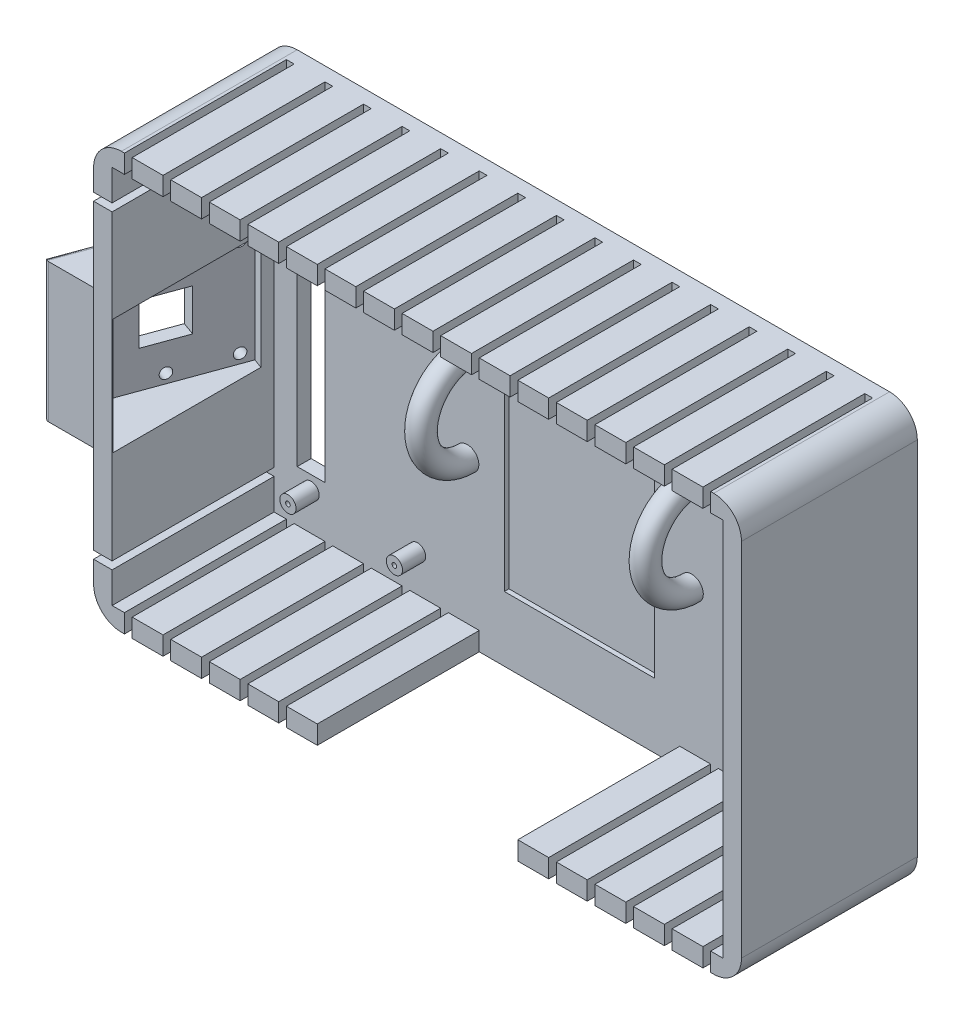
SolidWorks part; units mm, degrees
material "PLA"
ref_plane "Front Plane" through (0, 0, 0) normal (1, 0, 0) x (0, 1, 0)
ref_plane "Top Plane" through (0, 0, 0) normal (0, 0, 1) x (0, 1, 0)
ref_plane "Right Plane" through (0, 0, 0) normal (0, 1, 0) x (-1, 0, 0)
sketch "Sketch1" plane through (0, 0, 0) normal (0, 0, 1) x (0, 1, 0)
  line L0 (-45, 0) -> (45, 0) construction
  line L1 (45, -70) -> (-45, -70)
  line L2 (45, -70) -> (45, 70)
  line L3 (45, 70) -> (-45, 70)
  line L4 (-45, -70) -> (-45, 70)
  line L5 (0, 70) -> (0, -70) construction
  point P9 (0, 0)
  dimension "D1" = 140
  dimension "D2" = 90
extrude "Boss-Extrude1" add sketch "Sketch1" along normal blind 3
sketch "Sketch2" plane through (0, 0, 3) normal (0, 0, 1) x (1, 0, 0)
  line L0 (-70, 45) -> (-70, -45) construction
  line L1 (-16.25, 31) -> (16.25, 31)
  line L2 (-16.25, 31) -> (-16.25, -31)
  line L3 (-16.25, -31) -> (16.25, -31)
  line L4 (16.25, 31) -> (16.25, -31)
  line L6 (-70, 0) -> (-16.25, 0) construction
  line L7 (16.25, 0) -> (70, 0) construction
  line L8 (70, -45) -> (70, 45) construction
  line L9 (0, 31) -> (0, 45) construction
  line L10 (70, 45) -> (-70, 45) construction
  line L11 (0, -31) -> (0, -45) construction
  line L12 (-70, -45) -> (70, -45) construction
  dimension "D1" = 62
  dimension "D2" = 32.5
extrude "Cut-Extrude1" cut sketch "Sketch2" against normal blind 1
sketch "Sketch6" plane through (0, 0, 3) normal (0, 0, 1) x (1, 0, 0)
  line L0 (-70, -45) -> (70, -45) construction
  line L2 (-58, 25) -> (-58, 45) construction
  line L3 (70, 45) -> (-70, 45) construction
  circle A0 centre (-58, 25) radius 1.75
  circle A1 centre (-35, 25) radius 1.75
  circle A2 centre (-35, -33) radius 1.75
  circle A3 centre (-58, -33) radius 1.75
  circle A4 centre (-58, 25) radius 0.5
  circle A5 centre (-35, 25) radius 0.5
  circle A6 centre (-58, -33) radius 0.5
  circle A7 centre (-35, -33) radius 0.5
  dimension "D1" = 3.5
  dimension "D2" = 23
  dimension "D3" = 58
  dimension "D4" = 12
  dimension "D5" = 1
extrude "Boss-Extrude2" add sketch "Sketch6" along normal blind 5 contours A1 | A0 | A3 | A2 region at (-59.7005, 25, 3) region at (-36.7005, 25, 3) region at (-36.7005, -33, 3) region at (-59.7005, -33, 3)
extrude "Boss-Extrude3" add sketch "Sketch6<3>" along normal blind 4 contours A4 | A5 | A6 | A7 region at (-58, 25, 3) region at (-35, 25, 3) region at (-58, -33, 3) region at (-35, -33, 3)
sketch "Sketch6<3>" plane through (0, 0, 3) normal (0, 0, 1) x (1, 0, 0) same geometry as "Sketch6"
sketch "Sketch7" plane through (0, 0, 3) normal (0, 0, 1) x (1, 0, 0)
  line L0 (-61.6667, 45) -> (-61.6667, 41)
  line L1 (-70, 45) -> (-63.3333, 45)
  line L2 (-70, 45) -> (-70, 41)
  line L3 (-70, 41) -> (-63.3333, 41)
  line L4 (-63.3333, 45) -> (-63.3333, 41)
  line L5 (-61.6667, 45) -> (-55, 45)
  line L6 (-55, 45) -> (-55, 41)
  line L7 (-61.6667, 41) -> (-55, 41)
  line L8 (-53.3333, 45) -> (-53.3333, 41)
  line L9 (-53.3333, 45) -> (-46.6667, 45)
  line L10 (-46.6667, 45) -> (-46.6667, 41)
  line L11 (-53.3333, 41) -> (-46.6667, 41)
  line L12 (-45, 45) -> (-45, 41)
  line L13 (-45, 45) -> (-38.3333, 45)
  line L14 (-38.3333, 45) -> (-38.3333, 41)
  line L15 (-45, 41) -> (-38.3333, 41)
  line L16 (-36.6667, 45) -> (-36.6667, 41)
  line L17 (-36.6667, 45) -> (-30, 45)
  line L18 (-30, 45) -> (-30, 41)
  line L19 (-36.6667, 41) -> (-30, 41)
  line L20 (-28.3333, 45) -> (-28.3333, 41)
  line L21 (-28.3333, 45) -> (-21.6667, 45)
  line L22 (-21.6667, 45) -> (-21.6667, 41)
  line L23 (-28.3333, 41) -> (-21.6667, 41)
  line L24 (-20, 45) -> (-20, 41)
  line L25 (-20, 45) -> (-13.3333, 45)
  line L26 (-13.3333, 45) -> (-13.3333, 41)
  line L27 (-20, 41) -> (-13.3333, 41)
  line L28 (-11.6667, 45) -> (-11.6667, 41)
  line L29 (-11.6667, 45) -> (-5, 45)
  line L30 (-5, 45) -> (-5, 41)
  line L31 (-11.6667, 41) -> (-5, 41)
  line L32 (-3.3333, 45) -> (-3.3333, 41)
  line L33 (-3.3333, 45) -> (3.3333, 45)
  line L34 (3.3333, 45) -> (3.3333, 41)
  line L35 (-3.3333, 41) -> (3.3333, 41)
  line L36 (5, 45) -> (5, 41)
  line L37 (5, 45) -> (11.6667, 45)
  line L38 (11.6667, 45) -> (11.6667, 41)
  line L39 (5, 41) -> (11.6667, 41)
  line L40 (13.3333, 45) -> (13.3333, 41)
  line L41 (13.3333, 45) -> (20, 45)
  line L42 (20, 45) -> (20, 41)
  line L43 (13.3333, 41) -> (20, 41)
  line L44 (21.6667, 45) -> (21.6667, 41)
  line L45 (21.6667, 45) -> (28.3333, 45)
  line L46 (28.3333, 45) -> (28.3333, 41)
  line L47 (21.6667, 41) -> (28.3333, 41)
  line L48 (30, 45) -> (30, 41)
  line L49 (30, 45) -> (36.6667, 45)
  line L50 (36.6667, 45) -> (36.6667, 41)
  line L51 (30, 41) -> (36.6667, 41)
  line L52 (38.3333, 45) -> (38.3333, 41)
  line L53 (38.3333, 45) -> (45, 45)
  line L54 (45, 45) -> (45, 41)
  line L55 (38.3333, 41) -> (45, 41)
  line L56 (46.6667, 45) -> (46.6667, 41)
  line L57 (46.6667, 45) -> (53.3333, 45)
  line L58 (53.3333, 45) -> (53.3333, 41)
  line L59 (46.6667, 41) -> (53.3333, 41)
  line L60 (55, 45) -> (55, 41)
  line L61 (55, 45) -> (61.6667, 45)
  line L62 (61.6667, 45) -> (61.6667, 41)
  line L63 (55, 41) -> (61.6667, 41)
  line L64 (63.3333, 45) -> (63.3333, 41)
  line L65 (63.3333, 45) -> (70, 45)
  line L66 (70, 45) -> (70, 41)
  line L67 (63.3333, 41) -> (70, 41)
  line L112 (0, 0) -> (0, 18.2112) construction
  line L113 (0, 0) -> (-20.7335, 0) construction
  line L114 (13.3333, -45) -> (20, -45)
  line L115 (20, -45) -> (20, -41)
  line L116 (13.3333, -41) -> (20, -41)
  line L117 (13.3333, -45) -> (13.3333, -41)
  line L118 (21.6667, -45) -> (28.3333, -45)
  line L119 (28.3333, -45) -> (28.3333, -41)
  line L120 (21.6667, -41) -> (28.3333, -41)
  line L121 (21.6667, -45) -> (21.6667, -41)
  line L122 (30, -45) -> (36.6667, -45)
  line L123 (36.6667, -45) -> (36.6667, -41)
  line L124 (30, -41) -> (36.6667, -41)
  line L125 (30, -45) -> (30, -41)
  line L126 (38.3333, -45) -> (45, -45)
  line L127 (45, -45) -> (45, -41)
  line L128 (38.3333, -41) -> (45, -41)
  line L129 (38.3333, -45) -> (38.3333, -41)
  line L130 (46.6667, -45) -> (53.3333, -45)
  line L131 (53.3333, -45) -> (53.3333, -41)
  line L132 (46.6667, -41) -> (53.3333, -41)
  line L133 (46.6667, -45) -> (46.6667, -41)
  line L134 (55, -45) -> (61.6667, -45)
  line L135 (61.6667, -45) -> (61.6667, -41)
  line L136 (55, -41) -> (61.6667, -41)
  line L137 (55, -45) -> (55, -41)
  line L138 (63.3333, -45) -> (70, -45)
  line L139 (70, -45) -> (70, -41)
  line L140 (63.3333, -41) -> (70, -41)
  line L141 (63.3333, -45) -> (63.3333, -41)
  line L142 (5, -45) -> (11.6667, -45)
  line L143 (11.6667, -45) -> (11.6667, -41)
  line L144 (5, -41) -> (11.6667, -41)
  line L145 (5, -45) -> (5, -41)
  line L146 (-3.3333, -45) -> (3.3333, -45)
  line L147 (3.3333, -45) -> (3.3333, -41)
  line L148 (-3.3333, -41) -> (3.3333, -41)
  line L149 (-3.3333, -45) -> (-3.3333, -41)
  line L150 (-11.6667, -45) -> (-5, -45)
  line L151 (-5, -45) -> (-5, -41)
  line L152 (-11.6667, -41) -> (-5, -41)
  line L153 (-11.6667, -45) -> (-11.6667, -41)
  line L154 (-20, -45) -> (-13.3333, -45)
  line L155 (-13.3333, -45) -> (-13.3333, -41)
  line L156 (-20, -41) -> (-13.3333, -41)
  line L157 (-20, -45) -> (-20, -41)
  line L158 (-28.3333, -45) -> (-21.6667, -45)
  line L159 (-21.6667, -45) -> (-21.6667, -41)
  line L160 (-28.3333, -41) -> (-21.6667, -41)
  line L161 (-28.3333, -45) -> (-28.3333, -41)
  line L162 (-36.6667, -45) -> (-30, -45)
  line L163 (-30, -45) -> (-30, -41)
  line L164 (-36.6667, -41) -> (-30, -41)
  line L165 (-36.6667, -45) -> (-36.6667, -41)
  line L166 (-70, -41) -> (-63.3333, -41)
  line L167 (-63.3333, -45) -> (-63.3333, -41)
  line L168 (-70, -45) -> (-63.3333, -45)
  line L169 (-70, -45) -> (-70, -41)
  line L170 (-61.6667, -45) -> (-55, -45)
  line L171 (-55, -45) -> (-55, -41)
  line L172 (-61.6667, -41) -> (-55, -41)
  line L173 (-61.6667, -45) -> (-61.6667, -41)
  line L174 (-53.3333, -45) -> (-46.6667, -45)
  line L175 (-46.6667, -45) -> (-46.6667, -41)
  line L176 (-53.3333, -41) -> (-46.6667, -41)
  line L177 (-53.3333, -45) -> (-53.3333, -41)
  line L178 (-45, -45) -> (-38.3333, -45)
  line L179 (-38.3333, -45) -> (-38.3333, -41)
  line L180 (-45, -41) -> (-38.3333, -41)
  line L181 (-45, -45) -> (-45, -41)
  line L226 (-70, 32.6633) -> (-60.5263, 32.6633) construction
  line L227 (-70, -32.6633) -> (-61.2912, -32.6633) construction
  line L228 (-70, 45) -> (-70, -45) construction
  line L229 (-70, 32.6633) -> (-66, 32.6633)
  line L230 (-70, 32.6633) -> (-70, -32.6633)
  line L231 (-70, -32.6633) -> (-66, -32.6633)
  line L232 (-66, 32.6633) -> (-66, -32.6633)
  line L233 (70, 45) -> (66, 45)
  line L234 (70, 45) -> (70, -45)
  line L235 (70, -45) -> (66, -45)
  line L236 (66, 45) -> (66, -45)
  line L237 (-70, 41) -> (-66, 41)
  line L238 (-70, 41) -> (-70, 34.3333)
  line L239 (-70, 34.3333) -> (-66, 34.3333)
  line L240 (-66, 41) -> (-66, 34.3333)
  line L246 (-70, -34.3333) -> (-66, -34.3333)
  line L247 (-70, -34.3333) -> (-70, -41)
  line L248 (-70, -41) -> (-66, -41)
  line L249 (-66, -34.3333) -> (-66, -41)
  line M13 (70, 45) -> (-70, 45)
  line M14 (-70, 45) -> (-70, -45)
  line M15 (-70, -45) -> (70, -45)
  line M16 (70, -45) -> (70, 45)
  dimension "D1" = 6.6667
  dimension "D2" = 4
  dimension "D6" = 1.67
  dimension "D4" = 4
  dimension "D7" = 1.67
  dimension "D3" = 17
sketch "Sketch9" plane through (0, 0, 3) normal (0, 0, 1) x (1, 0, 0)
  line L0 (-36.3093, 0) -> (22.5747, 0) construction
  line L1 (0, 0) -> (0, 22.2066) construction
  line L2 (-16.25, 31) -> (-16.25, -31) construction
  circle A0 centre (-24.25, -10) radius 2.5
  circle A1 centre (24.25, -10) radius 2.5
  dimension "D1" = 5
  dimension "D2" = 10
  dimension "D3" = 8
revolve "Revolve3" add sketch "Sketch9" angle 180 about L0 reverse direction yes
extrude "Boss-Extrude8" add sketch "Sketch7" along normal blind 35 contours L167 L166 M15 M14 | L173 L171 L172 M15 | L177 L175 L176 M15 | L181 L179 L180 M15 | L165 L163 L164 M15 | L161 L159 L160 M15 | L157 L155 L156 M15 | L153 L151 L152 M15 | L149 L147 L148 M15 | L145 L143 L144 M15 | L121 L119 L120 M15 | L125 L123 L124 M15 | L129 L127 L128 M15 | L133 L131 L132 M15 | L137 L135 L136 M15 | L140 L236 L138 M16 | L67 L236 L140 M16 | L60 L63 L62 M13 | L56 L59 L58 M13 | L48 L51 L50 M13 | L32 L35 L34 M13 | L28 L31 L30 M13 | L24 L27 L26 M13 | L20 L23 L22 M13 | L16 L19 L18 M13 | L0 L7 L6 M13 | L4 L3 M13 M14 | L240 L237 L239 M14 | L116 L115 L114 L117 | L138 L141 L140 L139 | L66 L67 L64 L65 | L53 L54 L55 L52 | L44 L47 L46 L45 | L42 L43 L40 L41 | L36 L39 L38 L37 | L28 L31 L30 L29 | L13 L14 L15 L12 | L9 L10 L11 L8 | L230 L231 L232 L229 | L247 L248 L249 L246 region at (-58.3333, 43, 3) region at (-66.6667, 43, 3) region at (-68, 37.6667, 3) region at (-33.3333, 43, 3) region at (-25, 43, 3) region at (-66.6667, -43, 3) region at (-16.6667, 43, 3) region at (-58.3333, -43, 3) region at (-8.3333, 43, 3) region at (-50, -43, 3) region at (0, 43, 3) region at (-41.6667, -43, 3) region at (-33.3333, -43, 3) region at (-25, -43, 3) region at (-16.6667, -43, 3) region at (33.3333, 43, 3) region at (-8.3333, -43, 3) region at (0, -43, 3) region at (50, 43, 3) region at (8.3333, -43, 3) region at (58.3333, 43, 3) region at (25, -43, 3) region at (68, 0, 3) region at (68, -43, 3) region at (33.3333, -43, 3) region at (41.6667, -43, 3) region at (58.3333, -43, 3) region at (50, -43, 3)
sketch "Sketch18" plane through (0, 0, 0) normal (0, 1, 0) x (-1, 0, 0)
  line L0 (70, 36.5) -> (82.6547, 36.5)
  line L1 (70, 38) -> (70, 0) construction
  line L2 (82.6547, 36.5) -> (70, 1.7314)
  line L3 (70, 1.7314) -> (70, 36.5)
  line L4 (63.3333, 38) -> (70, 38) construction
  dimension "D1" = 20
  dimension "D2" = 37
  dimension "D3" = 1.5
extrude "Boss-Extrude9" add sketch "Sketch18" along normal blind 15 and the other way blind 15
sketch "Sketch19" plane through (-61.2551, 0, -22.295) normal (-0.9397, 0, -0.342) x (0, -1, 0)
  line L0 (-10.5, 43.0684) -> (-10.5, 30.5684) construction
  line L1 (4.5, 38.5684) -> (-4.5, 38.5684)
  line L2 (4.5, 38.5684) -> (4.5, 47.5684)
  line L3 (4.5, 47.5684) -> (-4.5, 47.5684)
  line L4 (-4.5, 38.5684) -> (-4.5, 47.5684)
  line L5 (10.5, 43.0684) -> (10.5, 30.5684) construction
  line L6 (-10.5, 43.0684) -> (10.5, 43.0684) construction
  line L7 (-10.5, 30.5684) -> (10.5, 30.5684) construction
  line L8 (0, 43.0684) -> (0, 30.5684) construction
  line L9 (-15, 25.5684) -> (-15, 62.5684) construction
  line L10 (15, 25.5684) -> (15, 62.5684) construction
  line L14 (15, 25.5684) -> (-15, 25.5684) construction
  circle A0 centre (-10.5, 43.0684) radius 1.15
  circle A1 centre (10.5, 43.0684) radius 1.15
  circle A2 centre (10.5, 30.5684) radius 1.15
  circle A3 centre (-10.5, 30.5684) radius 1.15
  circle A4 centre (0, 43.0684) radius 1
  point P15 (0, 47.5684)
  point P16 (4.5, 43.0684)
  dimension "D1" = 2.3
  dimension "D3" = 21
  dimension "D4" = 12.5
  dimension "D6" = 2
  dimension "D2" = 9
  dimension "D5" = 5
extrude "Cut-Extrude2" cut sketch "Sketch19" against normal up to next contours A4 | L4 L1 L2 L3 A4 | A0 | A3 | A2 | A1 region at (-74.4898, 0, 14.067) region at (-75.9854, 10.5, 18.176) region at (-75.9854, -10.5, 18.176) region at (-71.7101, -10.5, 6.4298) region at (-71.7101, 10.5, 6.4298) region at (-75.9854, 0, 18.176)
sketch "Sketch21" plane through (-61.2551, 0, -22.295) normal (-0.9397, 0, -0.342) x (0, -1, 0)
  line L0 (0, 62.5684) -> (0, 25.5684) construction
  line L1 (-12.5, 58.0684) -> (12.5, 58.0684)
  line L2 (-12.5, 58.0684) -> (-12.5, 28.0684)
  line L3 (-12.5, 28.0684) -> (12.5, 28.0684)
  line L4 (12.5, 58.0684) -> (12.5, 28.0684)
  line L5 (15, 62.5684) -> (-15, 62.5684) construction
  line L6 (15, 25.5684) -> (-15, 25.5684) construction
  circle A0 centre (-10.5, 30.5684) radius 1.15 construction
  dimension "D3" = 2.5
  dimension "D1" = 25
  dimension "D2" = 30
extrude "Cut-Extrude5" cut sketch "Sketch21" against normal up to next from offset 3 offset against normal yes
sketch "Sketch22" plane through (0, 0, 3) normal (0, 0, 1) x (1, 0, 0)
  line L0 (-16.25, 39) -> (16.25, 39)
  line L1 (-16.25, 39) -> (-16.25, 33)
  line L2 (16.25, 39) -> (16.25, 33)
  line L3 (-16.25, 33) -> (16.25, 33)
  line L4 (-16.25, 39) -> (16.25, 33) construction
  line L5 (16.25, 39) -> (-16.25, 33) construction
  line L6 (16.25, 31) -> (-16.25, 31) construction
  line L7 (-3.3333, 45) -> (-5, 45) construction
  point P1 (0, 36)
  dimension "D1" = 6
  dimension "D2" = 6
extrude "Cut-Extrude6" cut sketch "Sketch22" against normal through all
sketch "Sketch23" plane through (0, -45, 0) normal (0, -1, 0) x (1, 0, 0)
  line L0 (-20, 38) -> (-13.3333, 38) construction
  line L5 (-20, 38) -> (20, 38)
  line L6 (-20, 38) -> (-20, 3)
  line L7 (-20, 3) -> (20, 3)
  line L8 (20, 38) -> (20, 3)
extrude "Cut-Extrude7" cut sketch "Sketch23" against normal up to next (4 mm away) contours L8 L7 L6 L5
fillet "Fillet1" radius 6 4 edges at (70, 45, 19) (70, -45, 19) (-70, -45, 19) (-70, 45, 19)
sketch "Sketch24" plane through (0, 0, 3) normal (0, 0, 1) x (1, 0, 0)
  line L0 (-61, 22) -> (-61, -30)
  line L1 (-61, 22) -> (-55, 22)
  line L2 (-61, -30) -> (-55, -30)
  line L3 (-55, 22) -> (-55, -30)
  line L4 (-61, 22) -> (-55, -30) construction
  line L5 (-61, -30) -> (-55, 22) construction
  line L6 (-58, -33) -> (-58, 25) construction
  circle A2 centre (-58, 25) radius 0.5 construction
  circle A4 centre (-58, -33) radius 0.5 construction
  point P1 (-58, -4)
  dimension "D2" = 3
  dimension "D1" = 3
  dimension "D3" = 6
extrude "Cut-Extrude8" cut sketch "Sketch24" against normal through all
sketch "Sketch25" plane through (0, 0, 0) normal (0, 0, -1) x (1, 0, 0)
  line L0 (-28.95, -27.94) -> (-28.95, 27.94)
  line L1 (-28.95, -27.94) -> (-48, -27.94)
  line L2 (-28.95, 27.94) -> (-48, 27.94)
  line L3 (-48, -27.94) -> (-48, 27.94)
  line L4 (-28.95, -27.94) -> (-48, 27.94) construction
  line L5 (-28.95, 27.94) -> (-48, -27.94) construction
  line L8 (-70, 0) -> (19.1904, 0) construction
  line L9 (-70, -39) -> (-70, 39) construction
  line L10 (-64, 45) -> (64, 45) construction
  line L11 (64, -45) -> (-64, -45) construction
  line L12 (-55, 30) -> (-55, -22) construction
  circle A0 centre (-48, 27.94) radius 0.75
  circle A1 centre (-28.95, 27.94) radius 0.75
  circle A2 centre (-28.95, -27.94) radius 0.75
  circle A3 centre (-48, -27.94) radius 0.75
  circle A4 centre (-48, 27.94) radius 1.5
  circle A5 centre (-28.95, 27.94) radius 1.5
  circle A6 centre (-48, -27.94) radius 1.5
  circle A7 centre (-28.95, -27.94) radius 1.5
  point P1 (-38.475, 0)
  dimension "D1" = 1.5
  dimension "D5" = 3
  dimension "D2" = 55.88
  dimension "D3" = 19.05
  dimension "D4" = 7
extrude "Boss-Extrude10" add sketch "Sketch25" along normal blind 5 contours L3 A4 L2 A0 | L2 A4 L3 A0 | L2 A5 L0 A1 | L0 A1 L2 | L0 A5 L2 A1 | L3 A6 L1 A3 | L0 A7 L1 A2 | L1 A7 L0 A2 | L1 A6 L3 A3 | A1 region at (-29.6927, 27.1973, 0) region at (-28.9076, 26.815, 0) region at (-29.6927, -27.1973, 0) region at (-28.9076, -26.815, 0) region at (-49.0307, 28.9707, 0) region at (-47.2573, 27.1973, 0) region at (-28.8439, -28.0461, 0) region at (-47.2573, -27.1973, 0) region at (-46.875, -27.9824, 0)
fillet "Fillet4" radius 1 6 edges at (-70, -15, 19.1157) (-70, 15, 19.1157) (-76.3274, -15, 19.1157) (-70, 0, 1.7314) (-76.3274, 15, 19.1157) (-82.6547, 0, 36.5)
